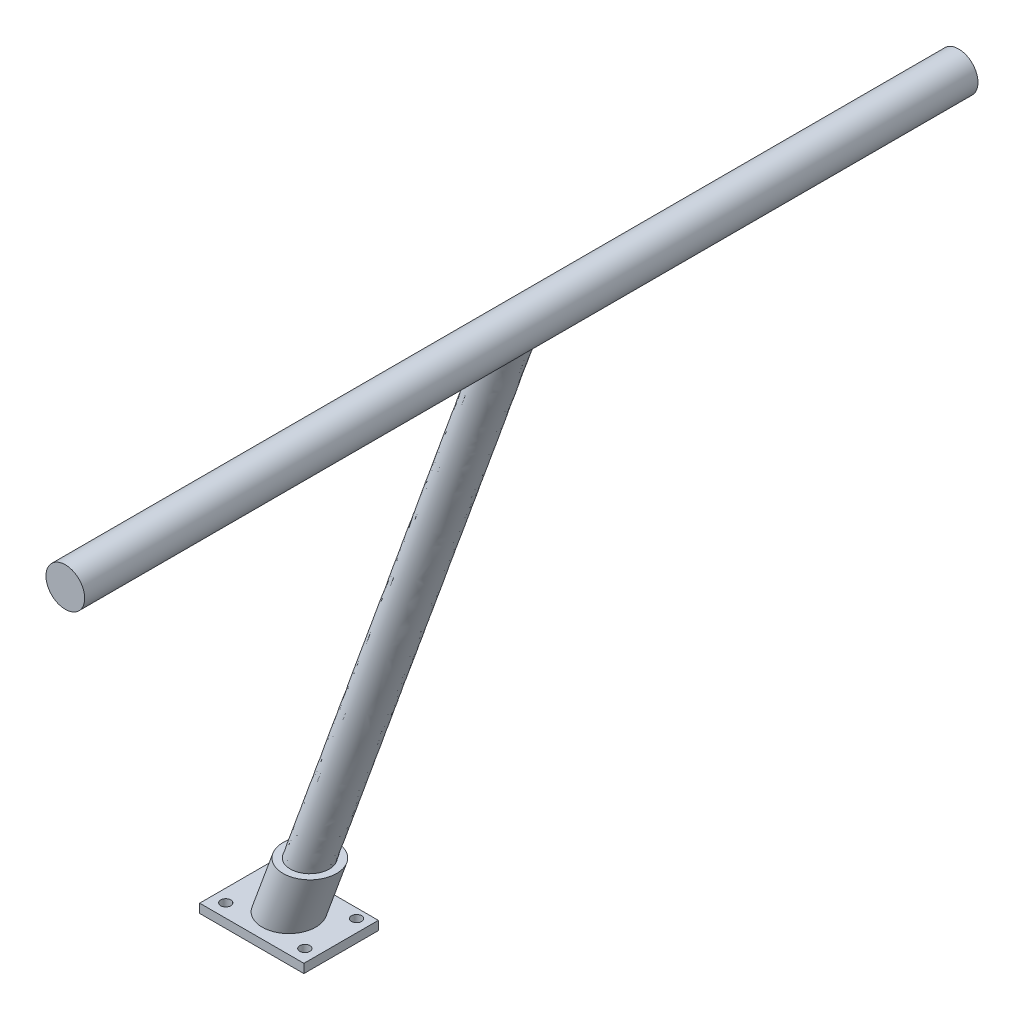
SolidWorks part; units mm, degrees
ref_plane "Ön Düzlem" through (0, 0, 0) normal (0, 0, 1) x (1, 0, 0)
ref_plane "Üst Düzlem" through (0, 0, 0) normal (0, 1, 0) x (1, 0, 0)
ref_plane "Sağ Düzlem" through (0, 0, 0) normal (1, 0, 0) x (0, 0, -1)
sketch "Çizim1" plane through (0, 0, 0) normal (0, 1, 0) x (1, 0, 0)
  line L1 (-17.5, 12.5) -> (17.5, 12.5)
  line L2 (-17.5, 12.5) -> (-17.5, -12.5)
  line L3 (-17.5, -12.5) -> (17.5, -12.5)
  line L4 (17.5, 12.5) -> (17.5, -12.5)
  line L5 (-17.5, 12.5) -> (17.5, -12.5) construction
  line L6 (-17.5, -12.5) -> (17.5, 12.5) construction
  point P0 (0, 0)
extrude "Yükseklik-Ekstrüzyon1" add sketch "Çizim1" along normal blind 3
sketch "Çizim2" plane through (0, 3, 0) normal (0, 1, 0) x (1, 0, 0)
  circle A0 centre (0, 0) radius 9
  circle A1 centre (0, 0) radius 6.5
sketch "Çizim5" plane through (0, 0, 0) normal (0, 0, 1) x (1, 0, 0)
  line L0 (0, 3) -> (7.0046, 22.1384)
  line L1 (9, 3) -> (-9, 3) construction
sweep "Süpür1" add profiles "Çizim2" path "Çizim5"
sketch "Çizim9" plane through (0, 3, 0) normal (0, 1, 0) x (1, 0, 0)
  circle A0 centre (0, 0) radius 6.5
sketch "Çizim11" plane through (0, 0, 0) normal (0, 0, 1) x (1, 0, 0)
  line L0 (0, 3) -> (74.8823, 209.8638)
  line L1 (6.5, 3) -> (-6.5, 3) construction
sweep "Süpür2" add profiles "Çizim9" path "Çizim11"
sketch "Çizim12" plane through (0, 209.8638, 0) normal (0, 1, 0) x (1, 0, 0)
  line L0 (74.8823, 150) -> (74.8823, -150)
  point P4 (74.8823, 0)
sketch "Çizim13" plane through (0, 0, 0) normal (0, 0, 1) x (1, 0, 0)
  circle A0 centre (74.8823, 209.8638) radius 6.5
extrude "Yükseklik-Ekstrüzyon3" add sketch "Çizim13" along normal mid plane 300
hole_wizard "M3 Boşluklu Delik1" positions "Çizim14" profile "Çizim15" hole size "M3" standard "ANSI Metrik" end condition through all
sketch "Çizim14" plane through (0, 3, 0) normal (0, 1, 0) x (1, 0, 0)
  point P0 (-13.209, -8.0302)
  point P2 (-13.209, 9.3558)
  point P4 (13.3452, -8.0302)
  point P6 (13.3452, 9.3558)
sketch "Çizim15" plane through (-13.209, 3, 8.0302) normal (1, 0, 0) x (0, 0, 1)
  line L0 (0, 0) -> (0, 3)
  line L1 (0, 3) -> (1.7, 3)
  line L2 (1.7, 3) -> (1.7, 0)
  line L5 (1.7, 0) -> (0, 0)
  line L11 (0, -6.35) -> (0, 107.95) construction
  dimension "Thru Hole Dia." = 3.4
  dimension "Thru Hole Depth" = 3
